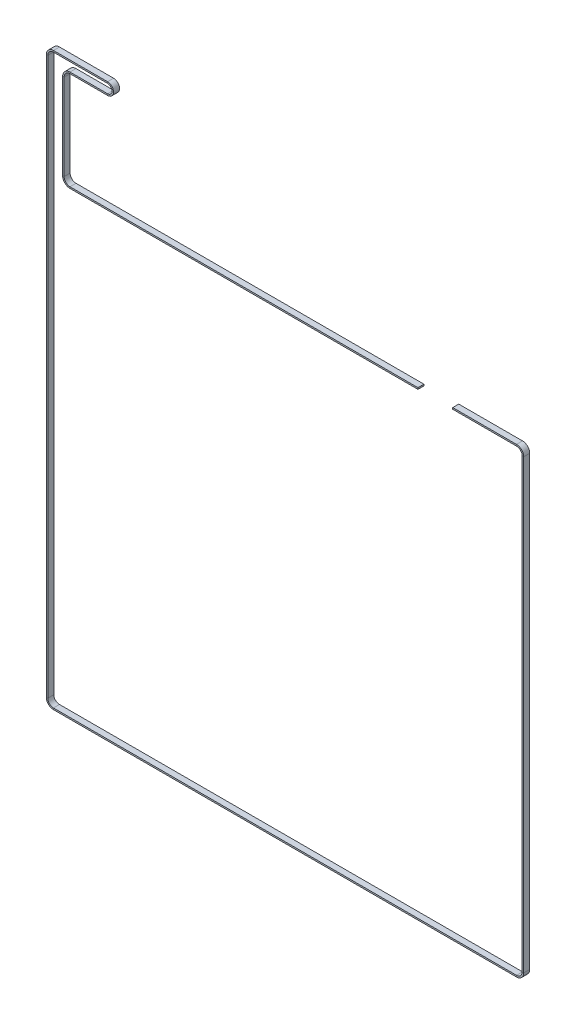
SolidWorks part; units mm, degrees
ref_plane "Front" through (0, 0, 0) normal (0, 0, 1) x (1, 0, 0)
ref_plane "Top" through (0, 0, 0) normal (0, 1, 0) x (1, 0, 0)
ref_plane "Right" through (0, 0, 0) normal (1, 0, 0) x (0, 0, -1)
sketch "Sketch1" plane through (0, -21, 4.45) normal (0, 0, 1) x (1, 0, 0)
  line L0 (10, 63.3) -> (47.5, 63.3)
  line L1 (47.5, 73.7) -> (-6.5, 73.7)
  line L2 (-12.875, 67.325) -> (-12.875, -488)
  line L3 (-6.5, -494.375) -> (455.5, -494.375)
  line L4 (461.875, -488) -> (461.875, -42.0466)
  line L5 (455.5, -35.6716) -> (391.85, -35.6716)
  line L6 (357.15, -39.2216) -> (357.15, -34.2216) construction
  line L7 (3.4, 56.7) -> (3.4, -29.2216)
  line L8 (10, -35.8216) -> (357.15, -35.8216)
  line L11 (391.85, -34.8216) -> (391.85, -31.2216) construction
  circle A0 centre (47.5, 68.5) radius 5.2 construction
  circle A1 centre (10, 56.7) radius 6.6 construction
  circle A2 centre (-6.5, 67.325) radius 6.375 construction
  circle A3 centre (10, -29.2216) radius 6.6 construction
  circle A4 centre (-6.5, -488) radius 6.375 construction
  circle A5 centre (455.5, -488) radius 6.375 construction
  circle A6 centre (455.5, -42.0466) radius 6.375 construction
  arc A7 (47.5, 73.7) -> (47.5, 63.3) centre (47.5, 68.5) cw
  arc A8 (10, 63.3) -> (3.4, 56.7) centre (10, 56.7) ccw
  arc A9 (-12.875, 67.325) -> (-6.5, 73.7) centre (-6.5, 67.325) cw
  arc A10 (-6.5, -494.375) -> (-12.875, -488) centre (-6.5, -488) cw
  arc A11 (455.5, -494.375) -> (461.875, -488) centre (455.5, -488) ccw
  arc A12 (461.875, -42.0466) -> (455.5, -35.6716) centre (455.5, -42.0466) ccw
  arc A13 (3.4, -29.2216) -> (10, -35.8216) centre (10, -29.2216) ccw
  circle A14 centre (-6.5, 67.325) radius 9 construction
  circle A15 centre (455.5, -42.0466) radius 5.9875 construction
  circle A16 centre (10, -29.2216) radius 5.9875 construction
  dimension "D1" = 12.75
ref_plane "Plane1" through (391.85, -56.6716, 4.45) normal (-1, 0, 0) x (0, 0, 1)
sketch "Sketch2" plane through (391.85, -56.6716, 4.45) normal (-1, 0, 0) x (0, 0, 1)
  line L1 (-3, 0.75) -> (3, 0.75)
  line L2 (-3, 0.75) -> (-3, -0.75)
  line L3 (-3, -0.75) -> (3, -0.75)
  line L4 (3, 0.75) -> (3, -0.75)
  line L5 (-3, 0.75) -> (3, -0.75) construction
  line L6 (-3, -0.75) -> (3, 0.75) construction
  point P0 (0, 0)
  dimension "D1" = 6
  dimension "D2" = 1.5
sweep "Sweep1" add profiles "Sketch2" path "Sketch1"
